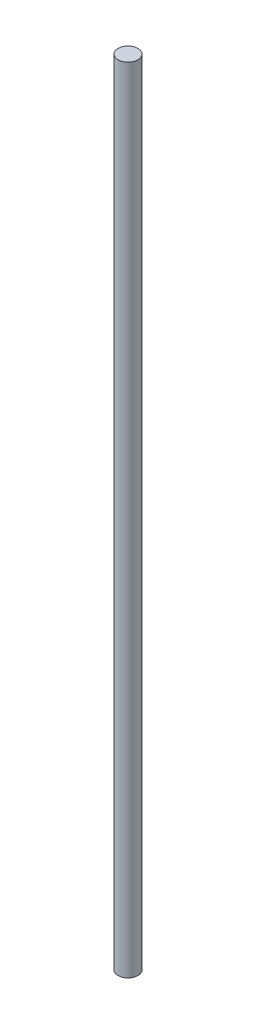
SolidWorks part; units mm, degrees
material "Alloy Steel (SS)"
ref_plane "Front Plane" through (0, 0, 0) normal (0, 0, 1) x (1, 0, 0)
ref_plane "Top Plane" through (0, 0, 0) normal (0, 1, 0) x (1, 0, 0)
ref_plane "Right Plane" through (0, 0, 0) normal (1, 0, 0) x (0, 0, -1)
sketch "Sketch2" plane through (0, 0, 0) normal (0, 1, 0) x (1, 0, 0)
  circle A0 centre (0, 0) radius 10
extrude "Boss-Extrude1" add sketch "Sketch2" along normal blind 800
ref_axis "Axis1" through (0, 1070.5834, 0) along (0, -1, 0)
